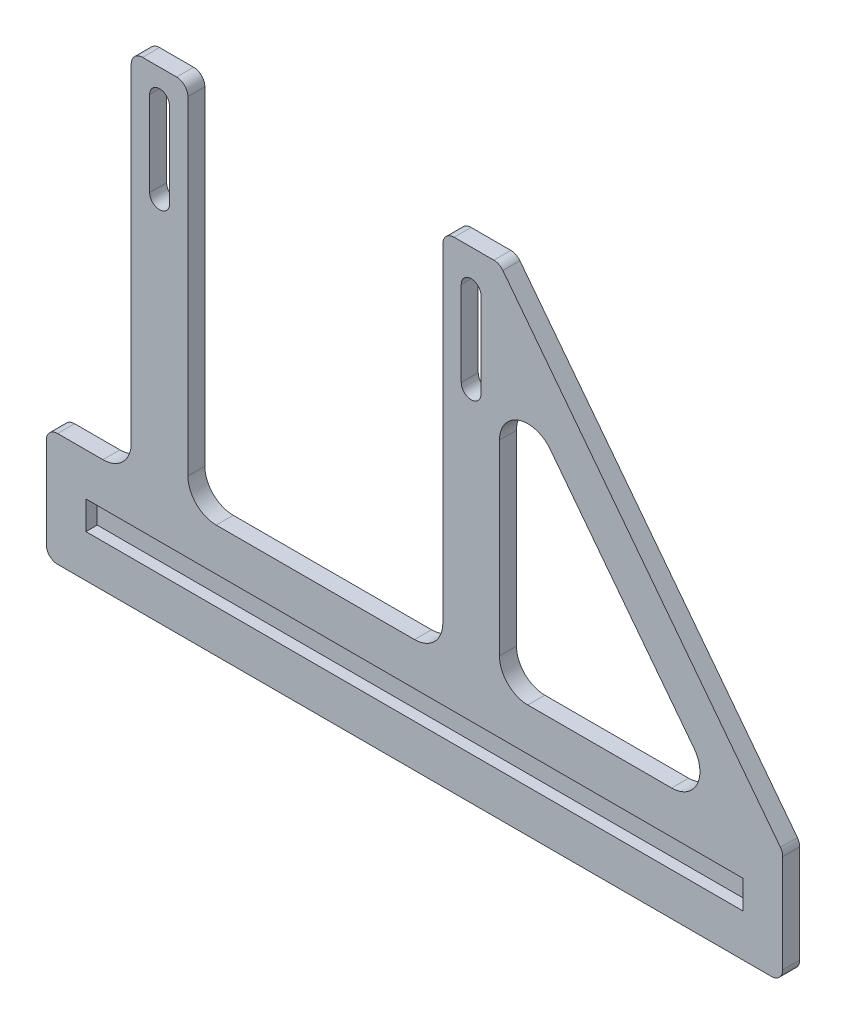
SolidWorks part; units mm, degrees
ref_plane "Alzado" through (0, 0, 0) normal (0, 0, 1) x (1, 0, 0)
ref_plane "Planta" through (0, 0, 0) normal (0, 1, 0) x (1, 0, 0)
ref_plane "Vista lateral" through (0, 0, 0) normal (1, 0, 0) x (0, 0, -1)
sketch "Croquis1" plane through (0, 0, 0) normal (0, 0, 1) x (1, 0, 0)
  line L0 (0, 94.9258) -> (0, -94.9258) construction
  line L2 (-40, 10) -> (-40, -10)
  line L3 (-40, -10) -> (40, -10)
  line L5 (-40, 10) -> (40, -10) construction
  line L6 (-40, -10) -> (40, 10) construction
  line L11 (40, 75) -> (30, 75)
  line L12 (30, 10) -> (30, 75)
  line L14 (40, 10) -> (40, 62.6991)
  line L15 (-20, 76.6393) -> (-20, 73.3607) construction
  line L16 (35, 75) -> (35, 47.1231) construction
  line L17 (-25, 10) -> (-40, 10)
  line L20 (35, 68.4155) -> (35, 53.4155) construction
  line L21 (33.25, 68.4155) -> (33.25, 53.4155)
  line L22 (36.75, 68.4155) -> (36.75, 53.4155)
  line L24 (-33, 2.5) -> (83, 2.5)
  line L25 (-33, 2.5) -> (-33, -2.5)
  line L26 (-33, -2.5) -> (83, -2.5)
  line L27 (83, 2.5) -> (83, -2.5)
  line L28 (90, 10) -> (40, 75)
  line L30 (40, 10) -> (80.5378, 10)
  line L32 (40, -10) -> (90, -10)
  line L33 (90, 10) -> (90, -10)
  line L35 (80.5378, 10) -> (40, 62.6991)
  line L36 (30, 10) -> (-15, 10)
  line L37 (-25, 10) -> (-25, 75)
  line L38 (-25, 75) -> (-15, 75)
  line L39 (-15, 10) -> (-15, 75)
  line L40 (-20, 69.9523) -> (-20, 54.9523) construction
  line L41 (-18.25, 69.9523) -> (-18.25, 54.9523)
  line L42 (-21.75, 69.9523) -> (-21.75, 54.9523)
  arc A2 (33.25, 68.4155) -> (36.75, 68.4155) centre (35, 68.4155) cw
  arc A3 (36.75, 53.4155) -> (33.25, 53.4155) centre (35, 53.4155) cw
  arc A4 (-18.25, 69.9523) -> (-21.75, 69.9523) centre (-20, 69.9523) ccw
  arc A5 (-21.75, 54.9523) -> (-18.25, 54.9523) centre (-20, 54.9523) ccw
  point P0 (0, 0)
  point P1 (0, 0)
  point P6 (0, 0)
  point P12 (0, 0)
  point P13 (0, 0)
  point P17 (-20, 75)
  point P19 (29.3249, 10)
  point P28 (35, 60.9155)
  point P33 (0, 0)
  point P51 (-20, 62.4523)
  dimension "D13" = 1.75
  dimension "D1" = 20
  dimension "D2" = 80
  dimension "D3" = 15
  dimension "D7" = 5
  dimension "D8" = 7
  dimension "D9" = 50
  dimension "D10" = 7
  dimension "D11" = 7.5
  dimension "D12" = 15
  dimension "D14" = 10
extrude "Saliente-Extruir1" add sketch "Croquis1" along normal blind 3
extrude "Saliente-Extruir2" add sketch "Croquis1<3>" along normal blind 1 contours L27 L24 L25 L26 region at (25, 0, 0)
sketch "Croquis1<3>" plane through (0, 0, 0) normal (0, 0, 1) x (1, 0, 0) same geometry as "Croquis1"
fillet "Redondeo1" radius 5 6 edges at (40, 62.6991, 1.5) (80.5378, 10, 1.5) (40, 10, 1.5) (-25, 10, 1.5) (30, 10, 1.5) (-15, 10, 1.5)
fillet "Redondeo2" radius 2 8 edges at (30, 75, 1.5) (90, 10, 1.5) (40, 75, 1.5) (90, -10, 1.5) (-40, 10, 1.5) (-40, -10, 1.5) (-25, 75, 1.5) (-15, 75, 1.5)
